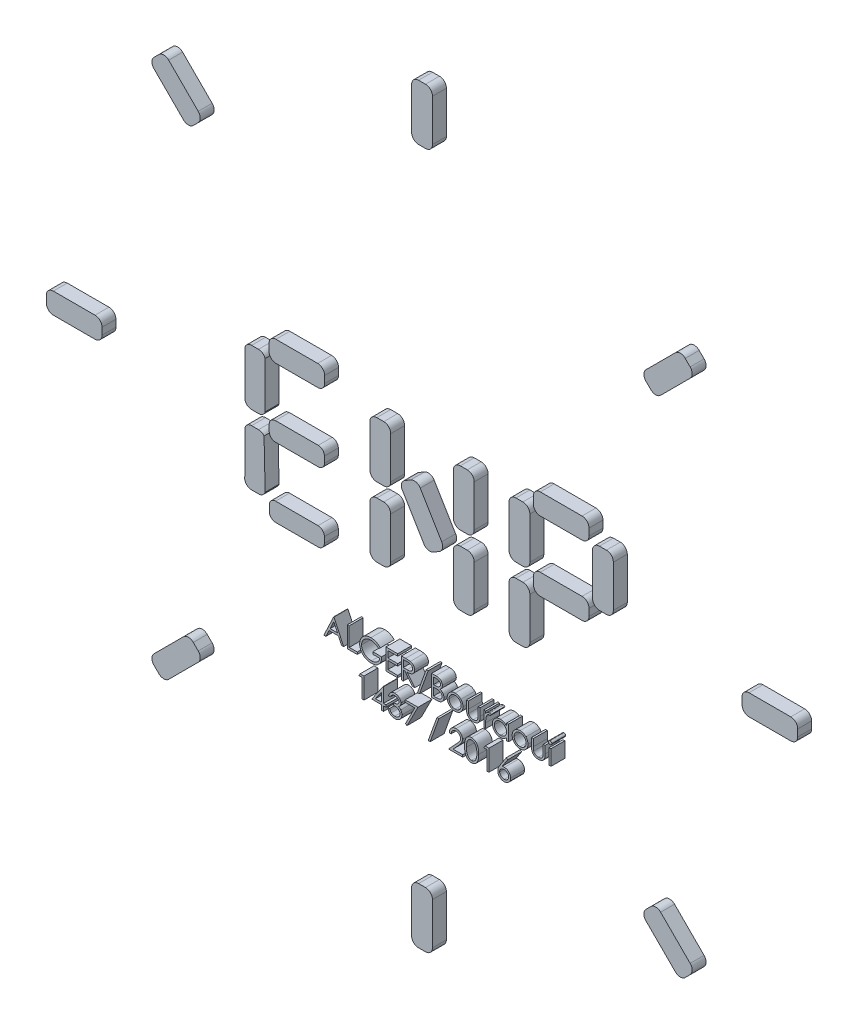
SolidWorks part; units mm, degrees
ref_plane "Plan de face" through (0, 0, 0) normal (0, 0, 1) x (1, 0, 0)
ref_plane "Plan de dessus" through (0, 0, 0) normal (0, 1, 0) x (1, 0, 0)
ref_plane "Plan de droite" through (0, 0, 0) normal (1, 0, 0) x (0, 0, -1)
sketch "Esquisse1" plane through (0, 0, 0) normal (0, 0, 1) x (1, 0, 0)
  line L0 (160.8668, -171.4734) -> (182.08, -192.6866)
  line L1 (235, -7.5) -> (265, -7.5)
  line L2 (230, -2.5) -> (230, 2.5)
  line L3 (235, 7.5) -> (265, 7.5)
  line L4 (270, -2.5) -> (270, 2.5)
  line L5 (230, -7.5) -> (270, 7.5) construction
  line L6 (230, 7.5) -> (270, -7.5) construction
  line L7 (160.8668, -164.4023) -> (164.4023, -160.8668)
  line L8 (171.4734, -160.8668) -> (192.6866, -182.08)
  line L9 (189.1511, -192.6866) -> (192.6866, -189.1511)
  line L10 (-7.5, -235) -> (-7.5, -265)
  line L11 (-2.5, -230) -> (2.5, -230)
  line L12 (7.5, -235) -> (7.5, -265)
  line L13 (-2.5, -270) -> (2.5, -270)
  line L14 (-171.4734, -160.8668) -> (-192.6866, -182.08)
  line L15 (-164.4023, -160.8668) -> (-160.8668, -164.4023)
  line L16 (-160.8668, -171.4734) -> (-182.08, -192.6866)
  line L17 (-192.6866, -189.1511) -> (-189.1511, -192.6866)
  line L18 (-235, 7.5) -> (-265, 7.5)
  line L19 (-230, 2.5) -> (-230, -2.5)
  line L20 (-235, -7.5) -> (-265, -7.5)
  line L21 (-270, 2.5) -> (-270, -2.5)
  line L22 (-160.8668, 171.4734) -> (-182.08, 192.6866)
  line L23 (-160.8668, 164.4023) -> (-164.4023, 160.8668)
  line L24 (-171.4734, 160.8668) -> (-192.6866, 182.08)
  line L25 (-189.1511, 192.6866) -> (-192.6866, 189.1511)
  line L26 (7.5, 235) -> (7.5, 265)
  line L27 (2.5, 230) -> (-2.5, 230)
  line L28 (-7.5, 235) -> (-7.5, 265)
  line L29 (2.5, 270) -> (-2.5, 270)
  line L30 (171.4734, 160.8668) -> (192.6866, 182.08)
  line L31 (164.4023, 160.8668) -> (160.8668, 164.4023)
  line L32 (160.8668, 171.4734) -> (182.08, 192.6866)
  line L33 (192.6866, 189.1511) -> (189.1511, 192.6866)
  line L34 (-105, 42.5) -> (-75, 42.5)
  line L35 (-110, 47.5) -> (-110, 52.5)
  line L36 (-105, 57.5) -> (-75, 57.5)
  line L37 (-70, 47.5) -> (-70, 52.5)
  line L38 (-105.2408, -56.6357) -> (-74.7592, -56.6357)
  line L39 (-109.8016, -52.0749) -> (-109.8016, -47.9251)
  line L40 (-105.2408, -43.3643) -> (-74.7592, -43.3643)
  line L41 (-70.1984, -52.0749) -> (-70.1984, -47.9251)
  line L42 (-105.3977, -6.704) -> (-74.6023, -6.704)
  line L43 (-109.8292, -2.2725) -> (-109.8292, 2.2725)
  line L44 (-105.3977, 6.704) -> (-74.6023, 6.704)
  line L45 (-70.1708, -2.2725) -> (-70.1708, 2.2725)
  line L46 (-112.7671, 8.3876) -> (-112.7671, 41.6124)
  line L47 (-117.5, 5) -> (-122.5, 5)
  line L48 (-127.2329, 8.3876) -> (-127.2329, 41.6124)
  line L49 (-117.5, 45) -> (-122.5, 45)
  line L50 (-112.7671, -41.6124) -> (-113.5427, -6.9439)
  line L51 (-117.5, -45) -> (-122.5, -45)
  line L52 (-127.2329, -38.3876) -> (-127.2329, -8.3876)
  line L53 (-117.5, -5) -> (-122.5, -5)
  line L54 (-120, 50) -> (-120, -50) construction
  line L55 (-120, -50) -> (-60, -50) construction
  line L56 (-60, -50) -> (-60, 50) construction
  line L57 (-60, 50) -> (-120, 50) construction
  line L58 (-120, 50) -> (-60, -50) construction
  line L59 (-60, -50) -> (-60, 50) construction
  line L60 (-60, 50) -> (-120, -50) construction
  line L61 (-30, 50) -> (-30, -50) construction
  line L62 (-30, -50) -> (30, -50) construction
  line L63 (30, -50) -> (30, 50) construction
  line L64 (30, 50) -> (-30, 50) construction
  line L65 (-30, 50) -> (30, -50) construction
  line L66 (30, -50) -> (30, 50) construction
  line L67 (30, 50) -> (-30, -50) construction
  line L68 (70, 50) -> (70, -50) construction
  line L69 (70, -50) -> (130, -50) construction
  line L70 (130, -50) -> (130, 50) construction
  line L71 (130, 50) -> (70, 50) construction
  line L72 (70, 50) -> (130, -50) construction
  line L73 (130, -50) -> (130, 50) construction
  line L74 (130, 50) -> (70, -50) construction
  line L75 (-75, 57.5) -> (-105, 42.5) construction
  line L76 (-105, 57.5) -> (-75, 42.5) construction
  line L77 (-105.2408, -56.6357) -> (-74.7592, -43.3643)
  line L78 (-105.2408, -43.3643) -> (-74.7592, -56.6357)
  line L79 (-105.3977, 6.704) -> (-74.6023, -6.704)
  line L80 (-74.6023, 6.704) -> (-105.3977, -6.704)
  line L81 (-112.7671, -41.6124) -> (-127.2329, -8.3876)
  line L82 (-113.5427, -6.9439) -> (-127.2329, -38.3876)
  line L83 (-127.2329, 41.6124) -> (-112.7671, 8.3876)
  line L84 (-127.2329, 8.3876) -> (-112.7671, 41.6124)
  line L85 (-120, 0) -> (-60, 0) construction
  line L86 (-60, 50) -> (-90, 50) construction
  line L87 (-90, 50) -> (-90, -50) construction
  line L88 (85, -7.5) -> (115, -7.5)
  line L89 (0, -50) -> (0, 0) construction
  line L90 (0, 0) -> (0, 50) construction
  line L91 (0, 50) -> (30, 50) construction
  line L92 (30, 50) -> (30, 0) construction
  line L93 (30, 0) -> (0, 0) construction
  line L94 (0, 0) -> (-30, 0) construction
  line L95 (-30, 0) -> (30, 0) construction
  line L96 (130, 0) -> (130, 50) construction
  line L97 (130, 50) -> (100, 50) construction
  line L98 (100, 50) -> (100, 0) construction
  line L99 (100, 0) -> (100, -50) construction
  line L100 (100, -50) -> (70, -50) construction
  line L101 (70, -50) -> (70, 0) construction
  line L102 (70, 0) -> (70, 50) construction
  line L103 (70, 0) -> (130, 0) construction
  line L104 (80, -2.5) -> (80, 2.5)
  line L105 (85, 7.5) -> (115, 7.5)
  line L106 (120, -2.5) -> (120, 2.5)
  line L107 (115, 7.5) -> (85, -7.5) construction
  line L108 (85, 7.5) -> (115, -7.5) construction
  line L109 (85, 42.5) -> (115, 42.5)
  line L110 (80, 47.5) -> (80, 52.5)
  line L111 (85, 57.5) -> (115, 57.5)
  line L112 (120, 47.5) -> (120, 52.5)
  line L113 (115, 57.5) -> (85, 42.5) construction
  line L114 (85, 57.5) -> (115, 42.5) construction
  line L115 (-14.1486, 9.0037) -> (1.2862, -16.7211)
  line L116 (-12.4336, 15.8636) -> (-8.1462, 18.4361)
  line L117 (-1.2862, 16.7211) -> (14.1486, -9.0037)
  line L118 (8.1462, -18.4361) -> (12.4336, -15.8636)
  line L119 (14.1486, -9.0037) -> (-14.1486, 9.0037) construction
  line L120 (-1.2862, 16.7211) -> (1.2862, -16.7211) construction
  line L127 (37.5, -40) -> (37.5, -10)
  line L128 (32.5, -45) -> (27.5, -45)
  line L129 (22.5, -40) -> (22.5, -10)
  line L130 (32.5, -5) -> (27.5, -5)
  line L131 (22.5, -10) -> (37.5, -40)
  line L132 (22.5, -40) -> (37.5, -10)
  line L133 (37.5, 10) -> (37.5, 40)
  line L134 (32.5, 5) -> (27.5, 5)
  line L135 (22.5, 10) -> (22.5, 40)
  line L136 (32.5, 45) -> (27.5, 45)
  line L137 (22.5, 40) -> (37.5, 10)
  line L138 (22.5, 10) -> (37.5, 40)
  line L139 (-22.5, -40) -> (-22.5, -10)
  line L140 (-27.5, -45) -> (-32.5, -45)
  line L141 (-37.5, -40) -> (-37.5, -10)
  line L142 (-27.5, -5) -> (-32.5, -5)
  line L143 (-37.5, -10) -> (-22.5, -40)
  line L144 (-37.5, -40) -> (-22.5, -10)
  line L145 (-22.5, 10) -> (-22.5, 40)
  line L146 (-27.5, 5) -> (-32.5, 5)
  line L147 (-37.5, 10) -> (-37.5, 40)
  line L148 (-27.5, 45) -> (-32.5, 45)
  line L149 (-37.5, 40) -> (-22.5, 10)
  line L150 (-37.5, 10) -> (-22.5, 40)
  line L151 (77.5, 10) -> (77.5, 40)
  line L152 (72.5, 5) -> (67.5, 5)
  line L153 (62.5, 10) -> (62.5, 40)
  line L154 (72.5, 45) -> (67.5, 45)
  line L155 (62.5, 40) -> (77.5, 10)
  line L156 (62.5, 10) -> (77.5, 40)
  line L181 (122.5, 40) -> (137.5, 10) construction
  line L182 (137.5, 10) -> (137.2861, 11.183) construction
  line L183 (137.5, 40) -> (122.5, 10) construction
  line L184 (137.5, 10) -> (137.5, 40)
  line L185 (132.5, 5) -> (127.5, 5)
  line L186 (122.5, 10) -> (122.5, 40)
  line L187 (132.5, 45) -> (127.5, 45)
  line L188 (122.5, 10) -> (123.1629, 8.5555) construction
  line L189 (62.5, -10) -> (77.5, -40) construction
  line L190 (77.5, -40) -> (77.2861, -38.817) construction
  line L191 (77.5, -10) -> (62.5, -40) construction
  line L192 (77.5, -40) -> (77.5, -10)
  line L193 (72.5, -45) -> (67.5, -45)
  line L194 (62.5, -40) -> (62.5, -10)
  line L195 (72.5, -5) -> (67.5, -5)
  line L196 (62.5, -40) -> (63.1629, -41.4445) construction
  circle A0 centre (0, 0) radius 250
  arc A1 (230, 2.5) -> (235, 7.5) centre (235, 2.5) cw
  arc A2 (265, -7.5) -> (270, -2.5) centre (265, -2.5) ccw
  arc A3 (235, -7.5) -> (230, -2.5) centre (235, -2.5) cw
  arc A4 (265, 7.5) -> (270, 2.5) centre (265, 2.5) cw
  arc A5 (192.6866, -182.08) -> (192.6866, -189.1511) centre (189.1511, -185.6155) cw
  arc A6 (182.08, -192.6866) -> (189.1511, -192.6866) centre (185.6155, -189.1511) ccw
  arc A7 (160.8668, -171.4734) -> (160.8668, -164.4023) centre (164.4023, -167.9379) cw
  arc A8 (164.4023, -160.8668) -> (171.4734, -160.8668) centre (167.9379, -164.4023) cw
  arc A9 (7.5, -265) -> (2.5, -270) centre (2.5, -265) cw
  arc A10 (-7.5, -265) -> (-2.5, -270) centre (-2.5, -265) ccw
  arc A11 (-7.5, -235) -> (-2.5, -230) centre (-2.5, -235) cw
  arc A12 (2.5, -230) -> (7.5, -235) centre (2.5, -235) cw
  arc A13 (-182.08, -192.6866) -> (-189.1511, -192.6866) centre (-185.6155, -189.1511) cw
  arc A14 (-192.6866, -182.08) -> (-192.6866, -189.1511) centre (-189.1511, -185.6155) ccw
  arc A15 (-171.4734, -160.8668) -> (-164.4023, -160.8668) centre (-167.9379, -164.4023) cw
  arc A16 (-160.8668, -164.4023) -> (-160.8668, -171.4734) centre (-164.4023, -167.9379) cw
  arc A17 (-265, -7.5) -> (-270, -2.5) centre (-265, -2.5) cw
  arc A18 (-265, 7.5) -> (-270, 2.5) centre (-265, 2.5) ccw
  arc A19 (-235, 7.5) -> (-230, 2.5) centre (-235, 2.5) cw
  arc A20 (-230, -2.5) -> (-235, -7.5) centre (-235, -2.5) cw
  arc A21 (-192.6866, 182.08) -> (-192.6866, 189.1511) centre (-189.1511, 185.6155) cw
  arc A22 (-182.08, 192.6866) -> (-189.1511, 192.6866) centre (-185.6155, 189.1511) ccw
  arc A23 (-160.8668, 171.4734) -> (-160.8668, 164.4023) centre (-164.4023, 167.9379) cw
  arc A24 (-164.4023, 160.8668) -> (-171.4734, 160.8668) centre (-167.9379, 164.4023) cw
  arc A25 (-7.5, 265) -> (-2.5, 270) centre (-2.5, 265) cw
  arc A26 (7.5, 265) -> (2.5, 270) centre (2.5, 265) ccw
  arc A27 (7.5, 235) -> (2.5, 230) centre (2.5, 235) cw
  arc A28 (-2.5, 230) -> (-7.5, 235) centre (-2.5, 235) cw
  arc A29 (182.08, 192.6866) -> (189.1511, 192.6866) centre (185.6155, 189.1511) cw
  arc A30 (192.6866, 182.08) -> (192.6866, 189.1511) centre (189.1511, 185.6155) ccw
  arc A31 (171.4734, 160.8668) -> (164.4023, 160.8668) centre (167.9379, 164.4023) cw
  arc A32 (160.8668, 164.4023) -> (160.8668, 171.4734) centre (164.4023, 167.9379) cw
  arc A33 (-110, 52.5) -> (-105, 57.5) centre (-105, 52.5) cw
  arc A34 (-75, 42.5) -> (-70, 47.5) centre (-75, 47.5) ccw
  arc A35 (-105, 42.5) -> (-110, 47.5) centre (-105, 47.5) cw
  arc A36 (-75, 57.5) -> (-70, 52.5) centre (-75, 52.5) cw
  arc A37 (-109.8016, -47.9251) -> (-105.2408, -43.3643) centre (-105.2408, -47.9251) cw
  arc A38 (-74.7592, -56.6357) -> (-70.1984, -52.0749) centre (-74.7592, -52.0749) ccw
  arc A39 (-105.2408, -56.6357) -> (-109.8016, -52.0749) centre (-105.2408, -52.0749) cw
  arc A40 (-74.7592, -43.3643) -> (-70.1984, -47.9251) centre (-74.7592, -47.9251) cw
  arc A41 (-109.8292, 2.2725) -> (-105.3977, 6.704) centre (-105.3977, 2.2725) cw
  arc A42 (-74.6023, -6.704) -> (-70.1708, -2.2725) centre (-74.6023, -2.2725) ccw
  arc A43 (-105.3977, -6.704) -> (-109.8292, -2.2725) centre (-105.3977, -2.2725) cw
  arc A44 (-74.6023, 6.704) -> (-70.1708, 2.2725) centre (-74.6023, 2.2725) cw
  arc A45 (-127.2329, 41.6124) -> (-122.5, 45) centre (-122.5, 40) cw
  arc A46 (-112.7671, 41.6124) -> (-117.5, 45) centre (-117.5, 40) ccw
  arc A47 (-112.7671, 8.3876) -> (-117.5, 5) centre (-117.5, 10) cw
  arc A48 (-122.5, 5) -> (-127.2329, 8.3876) centre (-122.5, 10) cw
  arc A49 (-127.2329, -8.3876) -> (-122.5, -5) centre (-122.5, -10) cw
  arc A50 (-113.5427, -6.9439) -> (-117.5, -5) centre (-117.5, -10) ccw
  arc A51 (-112.7671, -41.6124) -> (-117.5, -45) centre (-117.5, -40) cw
  arc A52 (-122.5, -45) -> (-127.2329, -38.3876) centre (-122.5, -40) cw
  arc A53 (80, 2.5) -> (85, 7.5) centre (85, 2.5) cw
  arc A54 (115, -7.5) -> (120, -2.5) centre (115, -2.5) ccw
  arc A55 (85, -7.5) -> (80, -2.5) centre (85, -2.5) cw
  arc A56 (115, 7.5) -> (120, 2.5) centre (115, 2.5) cw
  arc A57 (80, 52.5) -> (85, 57.5) centre (85, 52.5) cw
  arc A58 (115, 42.5) -> (120, 47.5) centre (115, 47.5) ccw
  arc A59 (85, 42.5) -> (80, 47.5) centre (85, 47.5) cw
  arc A60 (115, 57.5) -> (120, 52.5) centre (115, 52.5) cw
  arc A61 (-8.1462, 18.4361) -> (-1.2862, 16.7211) centre (-5.5737, 14.1486) cw
  arc A62 (1.2862, -16.7211) -> (8.1462, -18.4361) centre (5.5737, -14.1486) ccw
  arc A63 (-14.1486, 9.0037) -> (-12.4336, 15.8636) centre (-9.8612, 11.5762) cw
  arc A64 (14.1486, -9.0037) -> (12.4336, -15.8636) centre (9.8612, -11.5762) cw
  arc A69 (22.5, -10) -> (27.5, -5) centre (27.5, -10) cw
  arc A70 (37.5, -10) -> (32.5, -5) centre (32.5, -10) ccw
  arc A71 (37.5, -40) -> (32.5, -45) centre (32.5, -40) cw
  arc A72 (27.5, -45) -> (22.5, -40) centre (27.5, -40) cw
  arc A73 (22.5, 40) -> (27.5, 45) centre (27.5, 40) cw
  arc A74 (37.5, 40) -> (32.5, 45) centre (32.5, 40) ccw
  arc A75 (37.5, 10) -> (32.5, 5) centre (32.5, 10) cw
  arc A76 (27.5, 5) -> (22.5, 10) centre (27.5, 10) cw
  arc A77 (-37.5, -10) -> (-32.5, -5) centre (-32.5, -10) cw
  arc A78 (-22.5, -10) -> (-27.5, -5) centre (-27.5, -10) ccw
  arc A79 (-22.5, -40) -> (-27.5, -45) centre (-27.5, -40) cw
  arc A80 (-32.5, -45) -> (-37.5, -40) centre (-32.5, -40) cw
  arc A81 (-37.5, 40) -> (-32.5, 45) centre (-32.5, 40) cw
  arc A82 (-22.5, 40) -> (-27.5, 45) centre (-27.5, 40) ccw
  arc A83 (-22.5, 10) -> (-27.5, 5) centre (-27.5, 10) cw
  arc A84 (-32.5, 5) -> (-37.5, 10) centre (-32.5, 10) cw
  arc A85 (62.5, 40) -> (67.5, 45) centre (67.5, 40) cw
  arc A86 (77.5, 40) -> (72.5, 45) centre (72.5, 40) ccw
  arc A87 (77.5, 10) -> (72.5, 5) centre (72.5, 10) cw
  arc A88 (67.5, 5) -> (62.5, 10) centre (67.5, 10) cw
  arc A101 (122.5, 40) -> (127.5, 45) centre (127.5, 40) cw
  arc A102 (137.5, 40) -> (132.5, 45) centre (132.5, 40) ccw
  arc A103 (137.5, 10) -> (132.5, 5) centre (132.5, 10) cw
  arc A104 (127.5, 5) -> (122.5, 10) centre (127.5, 10) cw
  arc A105 (62.5, -10) -> (67.5, -5) centre (67.5, -10) cw
  arc A106 (77.5, -10) -> (72.5, -5) centre (72.5, -10) ccw
  arc A107 (77.5, -40) -> (72.5, -45) centre (72.5, -40) cw
  arc A108 (67.5, -45) -> (62.5, -40) centre (67.5, -40) cw
  text T0 "    ALGER\r\n1437 / 2016" font "Century Gothic" height 15
  point P3 (250, 0)
  point P107 (0, 0)
  point P122 (232.5556, -92.7136)
  point P123 (232.5556, -92.7136)
  point P125 (162.6346, -162.6346)
  point P180 (-90, 50)
  point P181 (-90, -50)
  point P182 (-90, 0)
  point P183 (-120, -25)
  point P184 (-120, 25)
  point P198 (-120, -25)
  point P200 (-120, 25)
  point P201 (-30, 25)
  point P202 (70, 25)
  point P203 (70, -25)
  point P204 (30, -25)
  point P205 (-30, -25)
  point P206 (-60, -25)
  point P207 (-60, 25)
  point P208 (30, 25)
  point P209 (130, 25)
  point P210 (130, -25)
  point P211 (-90, 0)
  point P213 (30, 0)
  point P214 (70, 0)
  point P226 (100, 0)
  point P239 (100, 50)
  point P252 (0, 0)
  point P294 (30, -25)
  point P295 (30, -25)
  point P308 (30, 25)
  point P309 (30, 25)
  point P322 (-30, -25)
  point P323 (-30, -25)
  point P336 (-30, 25)
  point P337 (-30, 25)
  point P350 (70, 25)
  point P351 (70, 25)
  point P389 (130, 25)
  point P402 (130, 25)
  point P403 (130, 25)
  point P406 (70, -25)
  point P419 (70, -25)
  point P420 (70, -25)
  point P421 (70, -25)
  point P422 (130, 25)
  dimension "D1" = 500
  dimension "D4" = 5
  dimension "D8" = 60
  dimension "D16" = 5
  dimension "D2" = 40
  dimension "D3" = 15
  dimension "D6" = 60
  dimension "D7" = 100
  dimension "D9" = 100
  dimension "D10" = 60
  dimension "D11" = 100
  dimension "D12" = 25
  dimension "D13" = 25
  dimension "D14" = 30
  dimension "D15" = 30
  dimension "D17" = 33.541
  dimension "D18" = 90
  dimension "D19" = 100
  dimension "D5" = 8
extrude "Boss.-Extru.1" add sketch "Esquisse1" along normal blind 10 contours A4 L3 A0 L1 A2 L4 | A3 L1 A0 L3 A1 L2 | L30 A30 L33 A29 L32 A0 | A32 L31 A31 L30 A0 L32 | A28 L27 A27 L26 A0 L28 | L26 A26 L29 A25 L28 A0 | L22 A22 L25 A21 L24 A0 | A24 L23 A23 L22 A0 L24 | A20 L19 A19 L18 A0 L20 | L18 A18 L21 A17 L20 A0 | L14 A14 L17 A13 L16 A0 | A16 L15 A15 L14 A0 L16 | L10 A10 L13 A9 L12 A0 | A12 L11 A11 L10 A0 L12 | A8 L7 A7 L0 A0 L8 | L0 A6 L9 A5 L8 A0 | A104 L185 A103 L184 A102 L187 A101 L186 | A56 L105 A53 L104 A55 L88 A54 L106 | L153 L156 L155 | L156 A86 L154 A85 L155 | A88 L152 A87 L155 L156 | L156 L155 L151 | A60 L111 A57 L110 A59 L109 A58 L112 | A108 L193 A107 L192 A106 L195 A105 L194 | L141 L144 L143 | L144 A78 L142 A77 L143 | A80 L140 A79 L143 L144 | L144 L143 L139 | L147 L150 L149 | L150 A82 L148 A81 L149 | A84 L146 A83 L149 L150 | L150 L149 L145 | A64 L117 A61 L116 A63 L115 A62 L118 | L138 A74 L136 A73 L137 | A76 L134 A75 L137 L138 | L138 L137 L133 | L132 A70 L130 A69 L131 | L132 L131 L127 | L135 L138 L137 | L129 L132 L131 | A72 L128 A71 L131 L132 | L84 L83 L46 | L84 A46 L49 A45 L83 | L48 L84 L83 | A48 L47 A47 L83 L84 | L82 A50 L53 A49 L81 | L82 L81 L52 | A52 L51 A51 L81 L82 | L50 L82 L81 | A36 L36 A33 L35 A35 L34 A34 L37 | A43 L80 L79 A41 L43 | L80 L44 L79 | A44 L80 L79 A42 L45 | L79 L80 L42 | A39 L77 L78 A37 L39 | L78 L77 L38 | L40 L78 L77 | A40 L77 L78 A38 L41 region at (169.9253, -169.9253, 0) region at (183.6014, -183.6014, 0) region at (0, -240.3107, 0) region at (0, -259.6517, 0) region at (259.6517, 0, 0) region at (240.3107, 0, 0) region at (-169.9253, -169.9253, 0) region at (-183.6014, -183.6014, 0) region at (-240.3107, 0, 0) region at (-259.6517, 0, 0) region at (183.6014, 183.6014, 0) region at (169.9253, 169.9253, 0) region at (-169.9253, 169.9253, 0) region at (-183.6014, 183.6014, 0) region at (0, 259.6517, 0) region at (0, 240.3107, 0) region at (-90, 50, 0) region at (-90, -54.4238, 0) region at (-102.5735, -50, 0) region at (-77.4265, -50, 0) region at (-90, -45.5762, 0) region at (-90, -4.4693, 0) region at (-102.6278, 0, 0) region at (-77.3722, 0, 0) region at (-90, 4.4693, 0) region at (-115.1781, 25, 0) region at (-120, 12.1488, 0) region at (-120, 37.8512, 0) region at (-124.8219, 25, 0) region at (-115.6706, -23.9813, 0) region at (-120.4819, -37.1637, 0) region at (-120.5529, -11.5117, 0) region at (-125.0559, -23.3876, 0) region at (100, 0, 0) region at (100, 50, 0) region at (0, 0, 0) region at (35, -25, 0) region at (30, -37.6429, 0) region at (30, -12.3571, 0) region at (25, -25, 0) region at (35, 25, 0) region at (30, 12.3571, 0) region at (30, 37.6429, 0) region at (25, 25, 0) region at (-25, -25, 0) region at (-30, -37.6429, 0) region at (-30, -12.3571, 0) region at (-35, -25, 0) region at (-25, 25, 0) region at (-30, 12.3571, 0) region at (-30, 37.6429, 0) region at (-35, 25, 0) region at (75, 25, 0) region at (70, 12.3571, 0) region at (70, 37.6429, 0) region at (65, 25, 0) region at (130, 25, 0) region at (70, -25, 0)
sketch "Esquisse2" plane through (0, 0, 0) normal (0, 0, 1) x (1, 0, 0)
  text T0 "ALGER/Bouraoui\r\n    1437 / 2016\r\n" font "Century Gothic" height 15
extrude "Boss.-Extru.2" add sketch "Esquisse2" along normal blind 10 separate body
